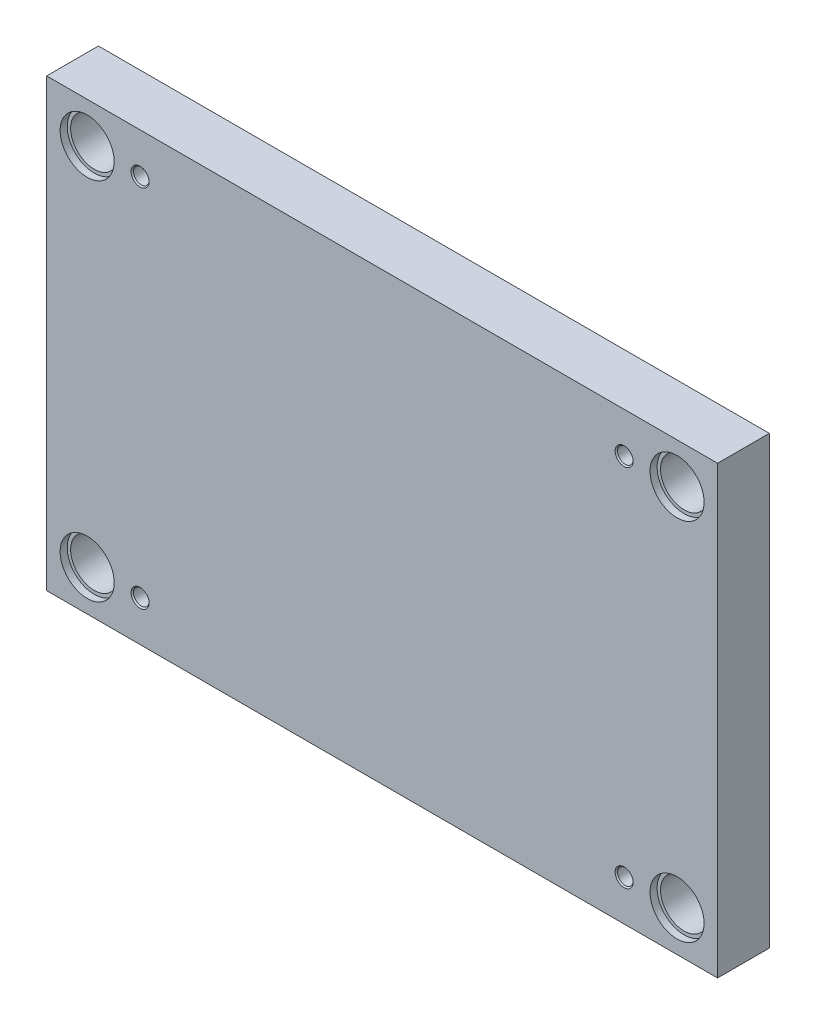
SolidWorks part; units mm, degrees
ref_plane "Płaszczyzna przednia" through (0, 0, 0) normal (0, 0, 1) x (1, 0, 0)
ref_plane "Płaszczyzna górna" through (0, 0, 0) normal (0, 1, 0) x (1, 0, 0)
ref_plane "Płaszczyzna prawa" through (0, 0, 0) normal (1, 0, 0) x (0, 0, -1)
sketch "Szkic1" plane through (0, 0, 0) normal (0, 0, 1) x (1, 0, 0)
  line L0 (-298, -198) -> (298, -198)
  line L1 (298, -198) -> (298, 198)
  line L2 (298, 198) -> (-298, 198)
  line L3 (-298, 198) -> (-298, -198)
extrude "Dodanie-wyciągnięcie1" add sketch "Szkic1" along normal blind 46
ref_plane "Płaszczyzna1" through (0, 0, 46) normal (0, 0, 1) x (1, 0, 0)
sketch "Szkic2" plane through (0, 0, 46) normal (0, 0, 1) x (1, 0, 0)
  circle A0 centre (262, 162) radius 21
extrude "Wytnij-wyciągnięcie1" cut sketch "Szkic2" against normal blind 46
sketch "Szkic3" plane through (0, 0, 46) normal (0, 0, 1) x (1, 0, 0)
  circle A0 centre (262, -162) radius 21
extrude "Wytnij-wyciągnięcie2" cut sketch "Szkic3" against normal blind 46
sketch "Szkic4" plane through (0, 0, 46) normal (0, 0, 1) x (1, 0, 0)
  circle A0 centre (-262, -162) radius 21
extrude "Wytnij-wyciągnięcie3" cut sketch "Szkic4" against normal blind 46
sketch "Szkic5" plane through (0, 0, 46) normal (0, 0, 1) x (1, 0, 0)
  circle A0 centre (-262, 162) radius 21
extrude "Wytnij-wyciągnięcie4" cut sketch "Szkic5" against normal blind 46
ref_plane "Płaszczyzna2" through (215, 0, 0) normal (1, 0, 0) x (0, 0, -1)
ref_plane "Płaszczyzna3" through (-215, 0, 0) normal (1, 0, 0) x (0, 0, -1)
sketch "Szkic6" plane through (0, 0, 46) normal (0, 0, 1) x (1, 0, 0)
  circle A0 centre (-262, 162) radius 24
extrude "Wytnij-wyciągnięcie5" cut sketch "Szkic6" against normal blind 6.3
sketch "Szkic7" plane through (0, 0, 46) normal (0, 0, 1) x (1, 0, 0)
  circle A0 centre (262, 162) radius 24
extrude "Wytnij-wyciągnięcie6" cut sketch "Szkic7" against normal blind 6.3
sketch "Szkic8" plane through (0, 0, 46) normal (0, 0, 1) x (1, 0, 0)
  circle A0 centre (-262, -162) radius 24
extrude "Wytnij-wyciągnięcie7" cut sketch "Szkic8" against normal blind 6.3
sketch "Szkic9" plane through (0, 0, 46) normal (0, 0, 1) x (1, 0, 0)
  circle A0 centre (262, -162) radius 24
extrude "Wytnij-wyciągnięcie8" cut sketch "Szkic9" against normal blind 6.3
sketch "Szkic10" plane through (-215, 0, 0) normal (1, 0, 0) x (0, 0, -1)
  line L0 (-46, 162) -> (-46, 170)
  line L1 (-46, 170) -> (-44.9175, 168.9175)
  line L2 (-44.9175, 168.9175) -> (-6, 168.9175)
  line L3 (-6, 168.9175) -> (-2.0062, 162)
  line L4 (-2.0062, 162) -> (-46, 162)
  line L5 (-2.0062, 162) -> (-46, 162) construction
revolve "Wycięcie-obrót1" cut sketch "Szkic10" angle 360 about L5 reverse direction yes
cosmetic thread "Oznaczenie gwintu1" parameters "D1"=30, "D2"=16
sketch "Szkic11" plane through (-215, 0, 0) normal (1, 0, 0) x (0, 0, -1)
  line L0 (-2.0062, -162) -> (-6, -168.9175)
  line L1 (-6, -168.9175) -> (-44.9175, -168.9175)
  line L2 (-44.9175, -168.9175) -> (-46, -170)
  line L3 (-46, -170) -> (-46, -162)
  line L4 (-46, -162) -> (-2.0062, -162)
  line L5 (-46, -162) -> (-2.0062, -162) construction
revolve "Wycięcie-obrót2" cut sketch "Szkic11" angle 360 about L5 reverse direction yes
cosmetic thread "Oznaczenie gwintu2" parameters "D1"=30, "D2"=16
sketch "Szkic12" plane through (215, 0, 0) normal (1, 0, 0) x (0, 0, -1)
  line L0 (-46, 162) -> (-46, 170)
  line L1 (-46, 170) -> (-44.9175, 168.9175)
  line L2 (-44.9175, 168.9175) -> (-6, 168.9175)
  line L3 (-6, 168.9175) -> (-2.0062, 162)
  line L4 (-2.0062, 162) -> (-46, 162)
  line L5 (-2.0062, 162) -> (-46, 162) construction
revolve "Wycięcie-obrót3" cut sketch "Szkic12" angle 360 about L5 reverse direction yes
cosmetic thread "Oznaczenie gwintu3" parameters "D1"=30, "D2"=16
sketch "Szkic13" plane through (215, 0, 0) normal (1, 0, 0) x (0, 0, -1)
  line L0 (-2.0062, -162) -> (-6, -168.9175)
  line L1 (-6, -168.9175) -> (-44.9175, -168.9175)
  line L2 (-44.9175, -168.9175) -> (-46, -170)
  line L3 (-46, -170) -> (-46, -162)
  line L4 (-46, -162) -> (-2.0062, -162)
  line L5 (-46, -162) -> (-2.0062, -162) construction
revolve "Wycięcie-obrót4" cut sketch "Szkic13" angle 360 about L5 reverse direction yes
cosmetic thread "Oznaczenie gwintu4" parameters "D1"=30, "D2"=16
ref_plane "Płaszczyzna4" through (0, 0, 46) normal (0, 0, 1) x (1, 0, 0)
ref_plane "IP1 XY" through (0, 0, 46) normal (0, 0, -1) x (-1, 0, 0)
ref_plane "IP1 XZ" through (0, 0, 0) normal (0, 1, 0) x (1, 0, 0)
ref_plane "IP1 YZ" through (0, 0, 0) normal (1, 0, 0) x (0, 0, -1)
ref_axis "IP1 X" through (-80.9, 0, 46) along (1, 0, 0)
ref_axis "IP1 Y" through (0, 50, 46) along (0, -1, 0)
ref_axis "IP1 Z" through (0, 0, -80.9) along (0, 0, 1)
sketch3d "IP1"
  point P0 (0, 0, 46)
ref_plane "IP2 XY" through (0, 0, 46) normal (0, 0, 1) x (1, 0, 0)
ref_plane "IP2 XZ" through (0, 162, 0) normal (0, -1, 0) x (-1, 0, 0)
ref_plane "IP2 YZ" through (-262, 0, 0) normal (1, 0, 0) x (0, 0, -1)
ref_axis "IP2 X" through (-80.9, 162, 46) along (1, 0, 0)
ref_axis "IP2 Y" through (-262, -50, 46) along (0, 1, 0)
ref_axis "IP2 Z" through (-262, 162, 80.9) along (0, 0, -1)
sketch3d "IP2"
  point P0 (-262, 162, 46)
ref_plane "IP3 XY" through (0, 0, 46) normal (0, 0, 1) x (1, 0, 0)
ref_plane "IP3 XZ" through (0, 162, 0) normal (0, -1, 0) x (-1, 0, 0)
ref_plane "IP3 YZ" through (262, 0, 0) normal (1, 0, 0) x (0, 0, -1)
ref_axis "IP3 X" through (-80.9, 162, 46) along (1, 0, 0)
ref_axis "IP3 Y" through (262, -50, 46) along (0, 1, 0)
ref_axis "IP3 Z" through (262, 162, 80.9) along (0, 0, -1)
sketch3d "IP3"
  point P0 (262, 162, 46)
ref_plane "IP4 XY" through (0, 0, 46) normal (0, 0, 1) x (1, 0, 0)
ref_plane "IP4 XZ" through (0, -162, 0) normal (0, -1, 0) x (-1, 0, 0)
ref_plane "IP4 YZ" through (-262, 0, 0) normal (1, 0, 0) x (0, 0, -1)
ref_axis "IP4 X" through (-80.9, -162, 46) along (1, 0, 0)
ref_axis "IP4 Y" through (-262, -50, 46) along (0, 1, 0)
ref_axis "IP4 Z" through (-262, -162, 80.9) along (0, 0, -1)
sketch3d "IP4"
  point P0 (-262, -162, 46)
ref_plane "IP5 XY" through (0, 0, 46) normal (0, 0, 1) x (1, 0, 0)
ref_plane "IP5 XZ" through (0, -162, 0) normal (0, -1, 0) x (-1, 0, 0)
ref_plane "IP5 YZ" through (262, 0, 0) normal (1, 0, 0) x (0, 0, -1)
ref_axis "IP5 X" through (-80.9, -162, 46) along (1, 0, 0)
ref_axis "IP5 Y" through (262, -50, 46) along (0, 1, 0)
ref_axis "IP5 Z" through (262, -162, 80.9) along (0, 0, -1)
sketch3d "IP5"
  point P0 (262, -162, 46)
